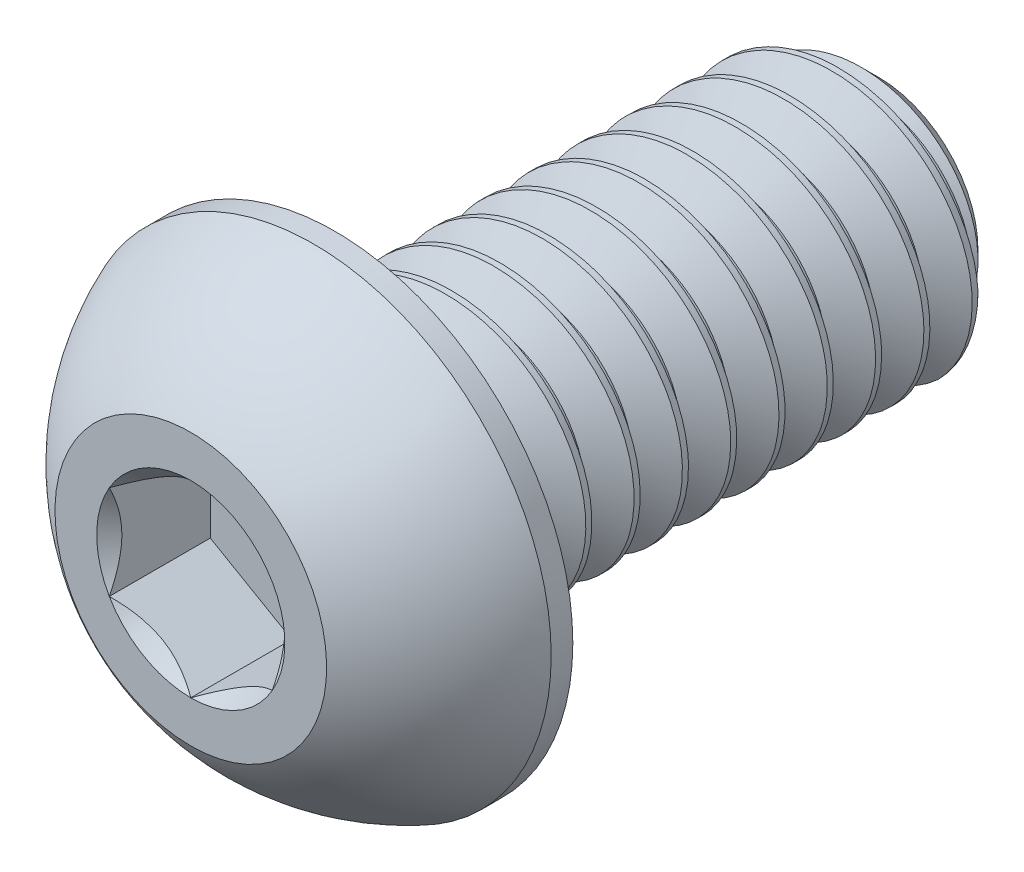
SolidWorks part; units mm, degrees
ref_plane "Front" through (0, 0, 0) normal (0, 0, 1) x (1, 0, 0)
ref_plane "Top" through (0, 0, 0) normal (0, 1, 0) x (1, 0, 0)
ref_plane "Right" through (0, 0, 0) normal (1, 0, 0) x (0, 0, -1)
sketch "Sketch1" plane through (0, 0, 0) normal (1, 0, 0) x (0, 0, -1)
  line L2 (4.2164, 3.9688) -> (20.0914, 3.9688)
  line L3 (20.0914, 3.9688) -> (20.0914, 0)
  line L4 (20.0914, 0) -> (4.2164, 0)
  line L6 (3.5839, 6.9469) -> (4.2164, 6.9469) construction
  line L7 (20.0914, 3.9688) -> (20.0914, -3.9687) construction
  line L8 (0, 0) -> (4.2164, 0) construction
  line L9 (4.2164, 6.9469) -> (4.2164, -6.9469) construction
  line L11 (4.2164, 3.9688) -> (4.2164, 0)
  line L13 (0, 2.3813) -> (0, -2.3813) construction
  line L14 (0, 2.3813) -> (0, 3.9688) construction
  arc A3 (0, 3.9688) -> (3.5839, 6.9469) centre (6.3273, 0) cw construction
  dimension "D1" = 0.6325
revolve "Revolve1" add sketch "Sketch1" angle 360 mid plane about L4
sketch "Sketch3" plane through (0, 0, -20.0914) normal (0, 0, -1) x (-1, 0, 0)
  circle A0 centre (0, 0) radius 3.9687
curve "Helix/Spiral1" pitch 1.4111 height 17.2861 radius 3.9687 centre (0, 0, -20.0914) axis (0, 0, 1) start towards (0, 1, 0)
sketch "Sketch2" plane through (0, 0, 0) normal (1, 0, 0) x (0, 0, -1)
  line L0 (20.0914, 3.9688) -> (21.3261, 3.9688)
  line L1 (21.3261, 3.9688) -> (20.797, 3.0522)
  line L2 (20.797, 3.0522) -> (20.6206, 3.0522)
  line L3 (20.6206, 3.0522) -> (20.0914, 3.9688)
  line L4 (20.356, 3.5105) -> (21.0615, 3.5105) construction
  dimension "D1" = 60
  dimension "D2" = 0.1764
  dimension "D3" = 0.7056
chamfer "Chamfer1" distance 1.0583 angle 45 1 edges at (0, 3.9688, -20.0914)
sweep "Cut-Sweep1" cut profiles "Sketch2" path "Helix/Spiral1" align with end faces yes
sketch "Sketch7" plane through (0, 0, 0) normal (1, 0, 0) x (0, 0, -1)
  line L6 (3.5839, 6.9469) -> (4.2164, 6.9469) construction
  line L8 (0, 0) -> (4.2164, 0) construction
  line L11 (4.2164, 6.9469) -> (4.2164, -6.9469) construction
  line L12 (3.5839, 6.9469) -> (4.2164, 6.9469)
  line L13 (0, 0) -> (4.2164, 0)
  line L14 (0, 2.3813) -> (0, -2.3813) construction
  line L15 (4.2164, 6.9469) -> (4.2164, 0)
  line L16 (0, 3.9688) -> (0, 0)
  arc A2 (3.5839, 6.9469) -> (0, 3.9688) centre (6.3273, 0) ccw construction
  arc A3 (3.5839, 6.9469) -> (0, 3.9688) centre (6.3273, 0) ccw
revolve "Revolve2" add sketch "Sketch7" angle 360 mid plane about L13
sketch "Sketch5" plane through (0, 0, 0) normal (0, 0, 1) x (1, 0, 0)
  line L1 (2.3813, -1.3748) -> (2.3813, 1.3748)
  line L2 (2.3813, 1.3748) -> (0, 2.7496)
  line L3 (0, 2.7496) -> (-2.3813, 1.3748)
  line L4 (-2.3813, 1.3748) -> (-2.3812, -1.3748)
  line L5 (-2.3812, -1.3748) -> (0, -2.7496)
  line L6 (0, -2.7496) -> (2.3813, -1.3748)
  circle A0 centre (0, 0) radius 2.3813 construction
extrude "Cut-Extrude2" cut sketch "Sketch5" against normal blind 2.9515
sketch "Sketch6" plane through (0, 0, 0) normal (0, 0, 1) x (1, 0, 0)
  circle A0 centre (0, 0) radius 2.7496
extrude "Cut-Extrude3" cut sketch "Sketch6" against normal blind 2.9515 draft 45
sketch "Sketch9" [suppressed] plane through (0, 0, -4.2164) normal (0, 0, 1) x (1, 0, 0)
  circle A2 centre (0, 0) radius 3.9687
extrude "Boss-Extrude2" [suppressed] add sketch "Sketch9" against normal offset from surface (9.525 mm away) 22.225 up to face at (0, 2.9104, -20.0914)
sketch "Sketch10" plane through (0, 0, 0) normal (1, 0, 0) x (0, 0, -1)
  line L0 (20.0914, 3.9688) -> (20.0914, -3.9687) construction
  point P0 (17.9747, -3.9687)
  dimension "D1" = 2.1167
equation "\"D3@Helix/Spiral1\" = \"Lg@Sketch1\" + \"D4@Helix/Spiral1\""
equation "\"D2@Sketch2\" = \"D4@Helix/Spiral1\" * .125"
equation "\"D3@Sketch2\" = \"D4@Helix/Spiral1\" * .5"
equation "\"D1@Chamfer1\" = \"D4@Helix/Spiral1\" * .75"
equation "\"D1@Cut-Extrude2\" = \"Head Ht@Sketch1\" * .7"
equation "\"D1@Sketch1\" = \"Head Ht@Sketch1\" * .15"
equation "\"D1@Sketch10\" = \"D4@Helix/Spiral1\" * 1.5"
equation "\"D1@Cut-Extrude3\" = \"D1@Cut-Extrude2\""
